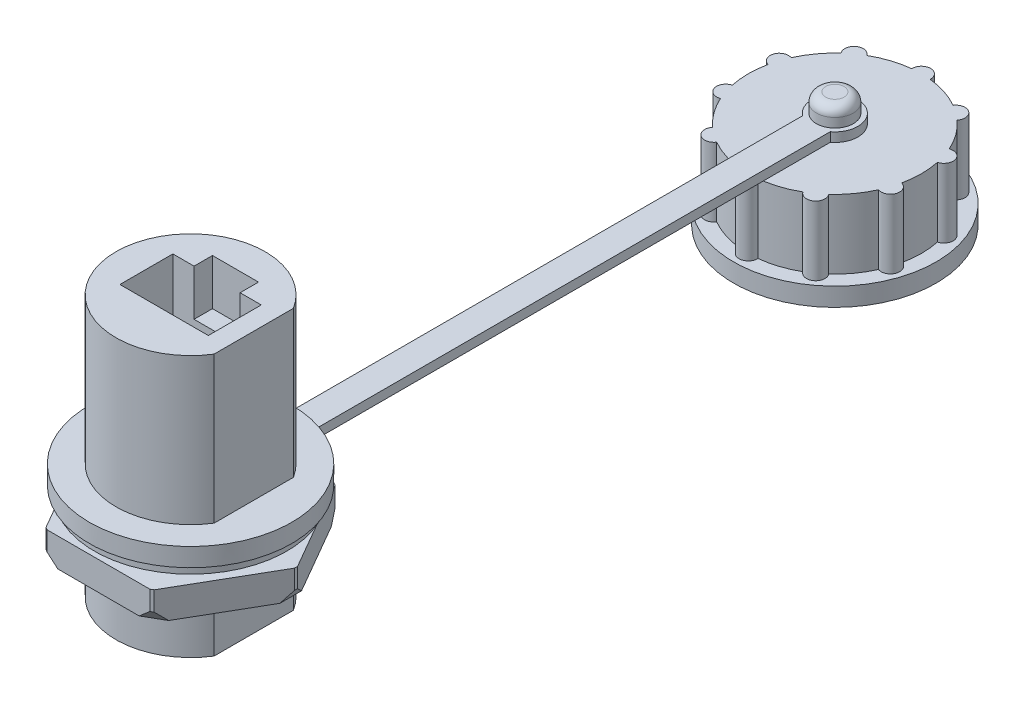
SolidWorks part; units mm, degrees
ref_plane "Front Plane" through (0, 0, 0) normal (0, 0, 1) x (1, 0, 0)
ref_plane "Top Plane" through (0, 0, 0) normal (0, 1, 0) x (1, 0, 0)
ref_plane "Right Plane" through (0, 0, 0) normal (1, 0, 0) x (0, 0, -1)
sketch "Sketch1" plane through (0, 0, 0) normal (0, 1, 0) x (1, 0, 0)
  line L0 (8.7122, -5.4699) -> (8.7122, 5.4699)
  arc A0 (8.7122, 5.4699) -> (8.7122, -5.4699) centre (0, 0) ccw
  point P1 (-10.287, 0)
  dimension "D1" = 20.574
  dimension "D2" = 18.9992
extrude "Boss-Extrude1" add sketch "Sketch1" along normal blind 13.335
sketch "Sketch2" plane through (0, 13.335, 0) normal (0, 1, 0) x (1, 0, 0)
  circle A0 centre (0, 0) radius 13.97
  dimension "D1" = 27.94
extrude "Boss-Extrude2" add sketch "Sketch2" along normal blind 2.54
extrude "Boss-Extrude3" add sketch "Sketch1<2>" along normal blind 36.068
sketch "Sketch1<2>" plane through (0, 0, 0) normal (0, 1, 0) x (1, 0, 0) same geometry as "Sketch1"
sketch "Sketch3" plane through (0, 13.335, 0) normal (0, -1, 0) x (1, 0, 0)
  line L1 (7.3323, 12.7) -> (-7.3323, 12.7)
  line L2 (-7.3323, 12.7) -> (-14.6647, 0)
  line L3 (-14.6647, 0) -> (-7.3323, -12.7)
  line L4 (-7.3323, -12.7) -> (7.3323, -12.7)
  line L5 (7.3323, -12.7) -> (14.6647, 0)
  line L6 (14.6647, 0) -> (7.3323, 12.7)
  circle A0 centre (0, 0) radius 10.287
  arc A1 (8.7122, 5.4699) -> (8.7122, -5.4699) centre (0, 0) ccw construction
  circle A2 centre (0, 0) radius 12.7 construction
  point P6 (0, 0)
  dimension "D1" = 25.4
extrude "Boss-Extrude4" add sketch "Sketch3" along normal blind 3.937 from offset 2.54
chamfer "Chamfer1" distance 0.254 angle 30 6 edges at (14.6647, 8.8265, 0) (7.3323, 8.8265, 12.7) (-7.3323, 8.8265, 12.7) (-14.6647, 8.8265, 0) (-7.3323, 8.8265, -12.7) (7.3323, 8.8265, -12.7) first distance on face at (10.9985, 8.8265, 6.35) first distance on face at (-10.9985, 8.8265, 6.35) first distance on face at (0, 8.8265, -12.7)
sketch "Sketch4" plane through (0, 0, 0) normal (0, -1, 0) x (1, 0, 0)
  line L1 (-6.096, -3.6512) -> (6.096, -3.6512)
  line L2 (-6.096, -3.6512) -> (-6.096, 3.6512)
  line L3 (-6.096, 3.6512) -> (6.096, 3.6512)
  line L4 (6.096, -3.6512) -> (6.096, 3.6512)
  line L5 (-6.096, -3.6512) -> (6.096, 3.6512) construction
  line L6 (-6.096, 3.6512) -> (6.096, -3.6512) construction
  point P0 (0, 0)
  dimension "D1" = 7.3025
  dimension "D2" = 12.192
extrude "Cut-Extrude1" cut sketch "Sketch4" against normal blind 10.922
sketch "Sketch5" plane through (0, 0, 0) normal (0, -1, 0) x (1, 0, 0)
  line L0 (-6.096, -3.6512) -> (6.096, -3.6512) construction
  line L1 (-3.175, -3.6512) -> (3.175, -3.6512)
  line L2 (-3.175, -3.6512) -> (-3.175, -6.1913)
  line L3 (-3.175, -6.1913) -> (3.175, -6.1913)
  line L4 (3.175, -3.6512) -> (3.175, -6.1913)
  point P6 (0, -3.6512)
  dimension "D1" = 6.35
  dimension "D2" = 2.54
extrude "Cut-Extrude2" cut sketch "Sketch5" against normal blind 6.35
ref_plane "Plane1" through (0, 18.034, 0) normal (0, -1, 0) x (-1, 0, 0)
mirror "Mirror1" about plane through (0, 18.034, 0) normal (0, -1, 0) of "Cut-Extrude2", "Cut-Extrude1"
sketch "Sketch6" plane through (0, 13.335, 0) normal (0, -1, 0) x (1, 0, 0)
  circle A0 centre (0, 0) radius 13.2671
  dimension "D1" = 26.5342
extrude "Boss-Extrude5" add sketch "Sketch6" along normal blind 1.27
sketch "Sketch7" plane through (0, 12.065, 0) normal (0, -1, 0) x (1, 0, 0)
  line L1 (-1.905, -10.1091) -> (1.905, -10.1091)
  line L2 (-1.905, -10.1091) -> (-1.905, -86.3091)
  line L4 (1.905, -10.1091) -> (1.905, -86.3091)
  arc A0 (8.7122, 5.4699) -> (8.7122, -5.4699) centre (0, 0) ccw construction
  arc A1 (-1.905, -86.3091) -> (1.905, -86.3091) centre (0, -88.8491) ccw
  point P8 (0, -10.1091)
  dimension "D3" = 3.175
  dimension "D1" = 3.81
  dimension "D2" = 76.2
  dimension "D4" = 2.54
extrude "Boss-Extrude6" add sketch "Sketch7" against normal up to surface (1.27 mm away) up to face at (0, 13.335, 13.2671)
sketch "Sketch8" plane through (0, 13.335, 0) normal (0, 1, 0) x (1, 0, 0)
  circle A0 centre (0, 88.8491) radius 2.54
  dimension "D1" = 5.08
extrude "Boss-Extrude7" add sketch "Sketch8" along normal blind 2.54
fillet "Fillet1" radius 1.27 1 edges at (0, 15.875, -86.3091)
sketch "Sketch9" plane through (0, 12.065, 0) normal (0, -1, 0) x (1, 0, 0)
  circle A0 centre (0, -88.8491) radius 11.938
  dimension "D1" = 23.876
extrude "Boss-Extrude8" add sketch "Sketch9" along normal blind 12.065
sketch "Sketch10" plane through (0, 0, 0) normal (0, -1, 0) x (1, 0, 0)
  circle A0 centre (0, -88.8491) radius 13.97
  dimension "D1" = 27.94
extrude "Boss-Extrude9" add sketch "Sketch10" against normal blind 2.54
sketch "Sketch11" plane through (0, 0, 0) normal (0, -1, 0) x (1, 0, 0)
  circle A0 centre (0, -88.8491) radius 10.287
  arc A1 (8.7122, 5.4699) -> (8.7122, -5.4699) centre (0, 0) ccw construction
extrude "Cut-Extrude3" cut sketch "Sketch11" against normal blind 6.223
sketch "Sketch12" plane through (0, 12.065, 0) normal (0, 1, 0) x (1, 0, 0)
  circle A0 centre (0, 100.7871) radius 1.27
  arc A1 (1.905, 77.064) -> (-1.905, 77.064) centre (0, 88.8491) ccw construction
  dimension "D1" = 2.54
extrude "Boss-Extrude10" add sketch "Sketch12" against normal up to surface (9.525 mm away) up to face at (0, 2.54, -100.7871)
pattern_circular "CirPattern1" count 10 over 360 about axis through (0, 12.065, -88.8491) along (0, -1, 0) of "Boss-Extrude10"
chamfer "Chamfer2" distance 1.27 angle 30 6 edges at (-7.2688, 6.858, -12.59) (7.2688, 6.858, -12.59) (14.5377, 6.858, 0) (7.2688, 6.858, 12.59) (-7.2688, 6.858, 12.59) (-14.5377, 6.858, 0) first distance on face at (-7.2688, 8.8265, -12.59) first distance on face at (7.2688, 8.8265, -12.59) first distance on face at (14.5377, 8.8265, 0) first distance on face at (7.2688, 8.8265, 12.59) first distance on face at (-7.2688, 8.8265, 12.59) first distance on face at (-14.5377, 8.8265, 0)
